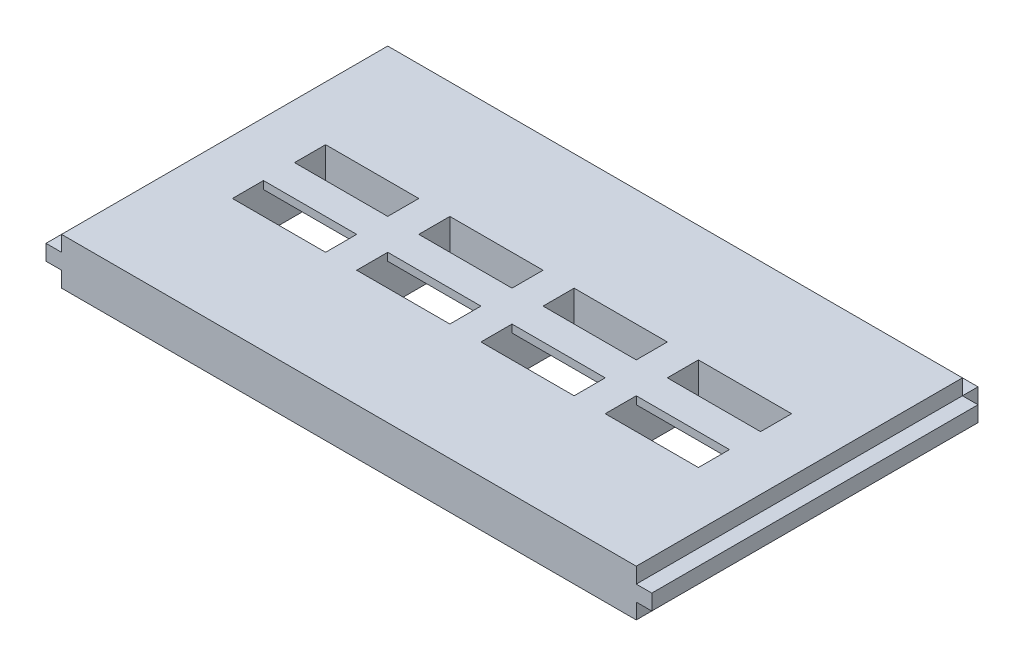
SolidWorks part; units mm, degrees
ref_plane "Спереди" through (0, 0, 0) normal (0, 0, 1) x (1, 0, 0)
ref_plane "Сверху" through (0, 0, 0) normal (0, 1, 0) x (1, 0, 0)
ref_plane "Справа" through (0, 0, 0) normal (1, 0, 0) x (0, 0, -1)
sketch "Эскиз1" plane through (0, 0, 0) normal (0, 1, 0) x (1, 0, 0)
  line L0 (18.5, -21) -> (18.5, 0) construction
  line L1 (0, 0) -> (37, 0)
  line L2 (0, 0) -> (0, -21)
  line L3 (0, -21) -> (37, -21)
  line L4 (37, 0) -> (37, -21)
  dimension "D1" = 37
  dimension "D2" = 21
extrude "Бобышка-Вытянуть1" add sketch "Эскиз1" along normal blind 3
sketch "Эскиз2" plane through (0, 0, 0) normal (0, -1, 0) x (1, 0, 0)
  line L0 (11.5, 13.5) -> (17.5, 13.5)
  line L1 (3.5, 13.5) -> (9.5, 13.5)
  line L2 (3.5, 13.5) -> (3.5, 7.5)
  line L3 (3.5, 7.5) -> (9.5, 7.5)
  line L4 (9.5, 13.5) -> (9.5, 7.5)
  line L5 (11.5, 13.5) -> (11.5, 7.5)
  line L6 (17.5, 13.5) -> (17.5, 7.5)
  line L7 (11.5, 7.5) -> (17.5, 7.5)
  line L8 (19.5, 13.5) -> (25.5, 13.5)
  line L9 (19.5, 13.5) -> (19.5, 7.5)
  line L10 (25.5, 13.5) -> (25.5, 7.5)
  line L11 (19.5, 7.5) -> (25.5, 7.5)
  line L12 (27.5, 13.5) -> (33.5, 13.5)
  line L13 (27.5, 13.5) -> (27.5, 7.5)
  line L14 (33.5, 13.5) -> (33.5, 7.5)
  line L15 (27.5, 7.5) -> (33.5, 7.5)
  line L16 (3.5, 13.5) -> (11.5, 13.5) construction
  line L17 (0, 0) -> (0, 21) construction
  line L18 (0, 21) -> (37, 21) construction
  line L19 (18.5, 21) -> (18.5, 0) construction
  line L20 (3.5, 11.5) -> (9.5, 11.5)
  line L21 (3.5, 11.5) -> (3.5, 9.5)
  line L22 (3.5, 9.5) -> (9.5, 9.5)
  line L23 (9.5, 11.5) -> (9.5, 9.5)
  line L24 (11.5, 11.5) -> (17.5, 11.5)
  line L25 (11.5, 11.5) -> (11.5, 9.5)
  line L26 (11.5, 9.5) -> (17.5, 9.5)
  line L27 (17.5, 11.5) -> (17.5, 9.5)
  line L28 (19.5, 11.5) -> (25.5, 11.5)
  line L29 (19.5, 11.5) -> (19.5, 9.5)
  line L30 (19.5, 9.5) -> (25.5, 9.5)
  line L31 (25.5, 11.5) -> (25.5, 9.5)
  line L32 (27.5, 11.5) -> (33.5, 11.5)
  line L33 (27.5, 11.5) -> (27.5, 9.5)
  line L34 (27.5, 9.5) -> (33.5, 9.5)
  line L35 (33.5, 11.5) -> (33.5, 9.5)
  line L36 (37, 0) -> (0, 0) construction
  line L37 (0, 10.5) -> (37, 10.5) construction
  line L38 (37, 21) -> (37, 0) construction
  dimension "D1" = 6
  dimension "D2" = 6
  dimension "D4" = 1
  dimension "D5" = 9
  dimension "D6" = 3
  dimension "D8" = 2
  dimension "D7" = 2
  dimension "D3" = 4
sketch "Эскиз5" plane through (37, 0, 0) normal (1, 0, 0) x (0, 0, -1)
  line L0 (-21, 3) -> (-21, 0) construction
  line L1 (-21, 2) -> (0, 2)
  line L2 (-21, 2) -> (-21, 1)
  line L3 (-21, 1) -> (0, 1)
  line L4 (0, 2) -> (0, 1)
  line L5 (0, 3) -> (0, 0) construction
  line L6 (-21, 3) -> (0, 3) construction
  dimension "D1" = 1
  dimension "D2" = 1
sketch "Эскиз7" plane through (0, 0, 0) normal (0, 0, -1) x (-1, 0, 0)
  line L0 (-37, 2) -> (-37, 1)
  line L1 (-37, 2) -> (0, 2)
  line L2 (-37, 1) -> (0, 1)
  line L3 (0, 2) -> (0, 1)
  line L4 (-37, 2) -> (-37, 1) construction
  line L5 (-37, 2) -> (-37, 1) construction
  line L6 (-37, 3) -> (-37, 0) construction
  line L7 (-37, 3) -> (0, 3) construction
  line L8 (0, 3) -> (0, 0) construction
  dimension "D1" = 1
  dimension "D2" = 1
sketch "Эскиз8" plane through (0, 0, 0) normal (-1, 0, 0) x (0, 0, 1)
  line L1 (0, 2) -> (21, 2)
  line L2 (0, 2) -> (0, 1)
  line L3 (0, 1) -> (21, 1)
  line L4 (21, 2) -> (21, 1)
extrude "Вырез-Вытянуть1" cut sketch "Эскиз2" against normal blind 10 contours L2 L20 L4 L1 | L22 L2 L3 L4 | L5 L24 L6 L0 | L26 L5 L7 L6 | L9 L28 L10 L8 | L30 L9 L11 L10 | L13 L32 L14 L12 | L34 L13 L15 L14 region at (14.5, 0, 12.5) region at (14.5, 0, 8.5) region at (6.5, 0, 12.5) region at (6.5, 0, 8.5) region at (22.5, 0, 12.5) region at (22.5, 0, 8.5) region at (30.5, 0, 12.5) region at (30.5, 0, 8.5)
extrude "Вырез-Вытянуть2" cut sketch "Эскиз2<10>" against normal blind 2.5 contours L2 L22 L4 L20 | L5 L26 L6 L24 | L9 L30 L10 L28 | L13 L34 L14 L32 region at (14.5, 0, 10.5) region at (6.5, 0, 10.5) region at (22.5, 0, 10.5) region at (30.5, 0, 10.5)
sketch "Эскиз2<10>" plane through (0, 0, 0) normal (0, -1, 0) x (1, 0, 0) same geometry as "Эскиз2"
extrude "Бобышка-Вытянуть2" add sketch "Эскиз5" along normal blind 1
extrude "Бобышка-Вытянуть3" add sketch "Эскиз7" along normal blind 1
extrude "Бобышка-Вытянуть4" add sketch "Эскиз8" along normal blind 1
